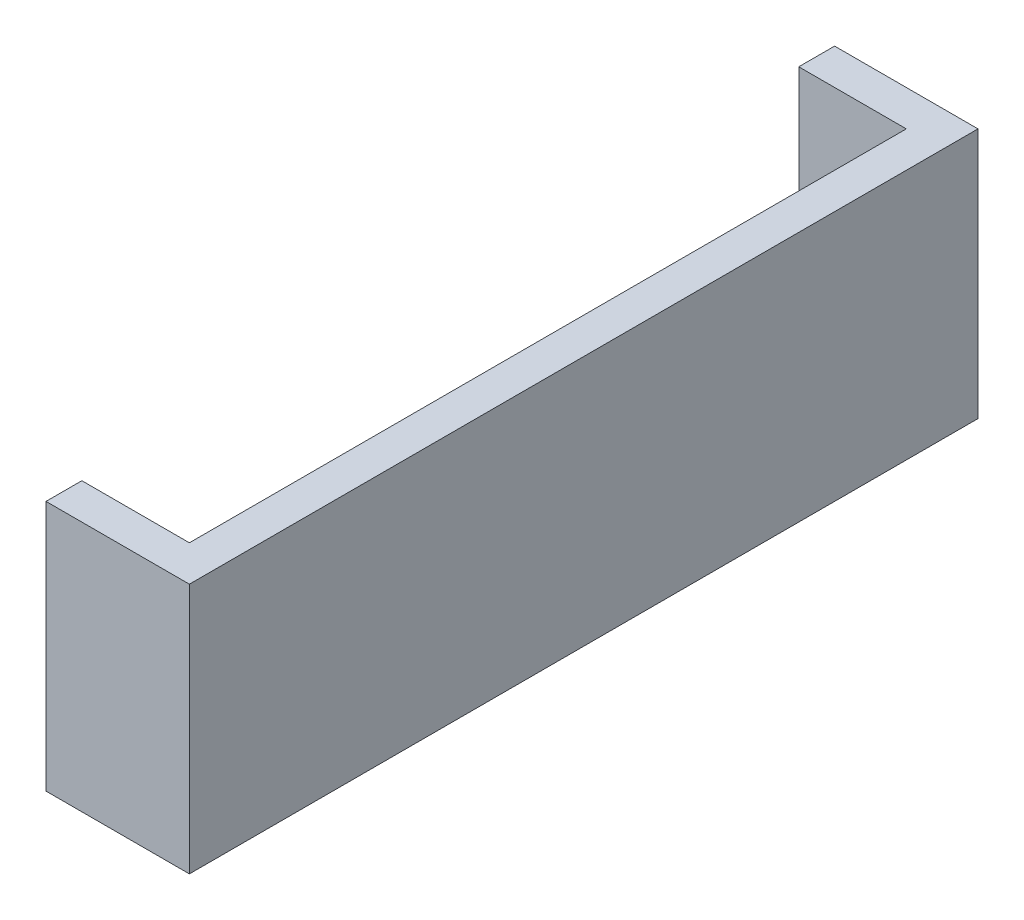
SolidWorks part; units mm, degrees
ref_plane "Front Plane" through (0, 0, 0) normal (0, 0, 1) x (1, 0, 0)
ref_plane "Top Plane" through (0, 0, 0) normal (0, 1, 0) x (1, 0, 0)
ref_plane "Right Plane" through (0, 0, 0) normal (1, 0, 0) x (0, 0, -1)
sketch "Sketch1" plane through (0, 0, 0) normal (0, 1, 0) x (1, 0, 0)
  line L1 (-12.7, -69.85) -> (12.7, -69.85)
  line L2 (-12.7, -69.85) -> (-12.7, 69.85)
  line L3 (-12.7, 69.85) -> (12.7, 69.85)
  line L4 (12.7, -69.85) -> (12.7, 69.85)
  line L5 (-12.7, -69.85) -> (12.7, 69.85) construction
  line L6 (-12.7, 69.85) -> (12.7, -69.85) construction
  point P0 (0, 0)
  dimension "D1" = 25.4
  dimension "D2" = 139.7
extrude "Boss-Extrude1" add sketch "Sketch1" along normal blind 6.35
sketch "Sketch3" plane through (0, 6.35, 0) normal (0, 1, 0) x (1, 0, 0)
  line L0 (12.7, -69.85) -> (12.7, 69.85) construction
  line L1 (-12.7, 69.85) -> (12.7, 69.85)
  line L2 (-12.7, 69.85) -> (-12.7, 63.5)
  line L3 (-12.7, 63.5) -> (12.7, 63.5)
  line L4 (12.7, 69.85) -> (12.7, 63.5)
  line L6 (-12.7, -69.85) -> (12.7, -69.85)
  line L7 (-12.7, -69.85) -> (-12.7, -63.5)
  line L8 (-12.7, -63.5) -> (12.7, -63.5)
  line L9 (12.7, -69.85) -> (12.7, -63.5)
  dimension "D1" = 6.35
extrude "Boss-Extrude2" add sketch "Sketch3" along normal blind 38.1
sketch "Sketch6" plane through (0, 6.35, 0) normal (0, 1, 0) x (1, 0, 0)
  line L0 (12.7, -63.5) -> (12.7, 63.5) construction
  line L1 (12.7, 50.8) -> (19.05, 50.8)
  line L2 (12.7, 50.8) -> (12.7, 38.1)
  line L3 (12.7, 38.1) -> (19.05, 38.1)
  line L5 (12.7, 69.85) -> (-12.7, 69.85) construction
  line L6 (19.05, 57.15) -> (25.4, 57.15)
  line L7 (19.05, 57.15) -> (19.05, 50.8)
  line L8 (19.05, 31.75) -> (25.4, 31.75)
  line L9 (25.4, 57.15) -> (25.4, 31.75)
  line L10 (19.05, 38.1) -> (19.05, 31.75)
  point P10 (25.4, 44.45)
  point P11 (12.7, 44.45)
  dimension "D1" = 6.35
  dimension "D2" = 12.7
  dimension "D3" = 25.4
  dimension "D4" = 6.35
  dimension "D5" = 25.4
extrude "Boss-Extrude3" add sketch "Sketch6" against normal up to surface (6.35 mm away) up to face at (0, 0, 0)
sketch "Sketch7" plane through (0, 6.35, 0) normal (0, 1, 0) x (1, 0, 0)
  line L0 (-12.7, 63.5) -> (-12.7, -63.5) construction
  line L1 (-12.7, 50.8) -> (-6.35, 50.8)
  line L2 (-12.7, 50.8) -> (-12.7, 38.1)
  line L3 (-12.7, 38.1) -> (-6.35, 38.1)
  line L5 (-6.35, 38.1) -> (-6.35, 31.75)
  line L6 (0, 57.15) -> (-6.35, 57.15)
  line L7 (0, 57.15) -> (0, 31.75)
  line L8 (0, 31.75) -> (-6.35, 31.75)
  line L9 (-6.35, 57.15) -> (-6.35, 50.8)
  line L10 (19.05, 50.8) -> (12.7, 50.8) construction
  line L11 (25.4, 57.15) -> (19.05, 57.15) construction
  line L12 (19.05, 57.15) -> (19.05, 50.8) construction
  line L13 (25.4, 31.75) -> (25.4, 57.15) construction
extrude "Cut-Extrude2" cut sketch "Sketch7" against normal through all
mirror "Mirror1" about plane through (0, 0, 0) normal (0, 0, 1) of "Boss-Extrude3", "Cut-Extrude2"
sketch "Sketch8" plane through (0, 6.35, 0) normal (0, 1, 0) x (1, 0, 0)
  line L0 (-12.7, -69.85) -> (12.7, -69.85) construction
  line L1 (12.7, 69.85) -> (25.4, 69.85)
  line L2 (12.7, 69.85) -> (12.7, -69.85)
  line L3 (12.7, -69.85) -> (25.4, -69.85)
  line L4 (25.4, 69.85) -> (25.4, -69.85)
  line L5 (25.4, 31.75) -> (25.4, 57.15) construction
extrude "Cut-Extrude3" cut sketch "Sketch8" against normal through all
sketch "Sketch9" plane through (0, 6.35, 0) normal (0, 1, 0) x (1, 0, 0)
  line L0 (12.7, -63.5) -> (-12.7, -63.5) construction
  line L1 (12.7, 63.5) -> (6.35, 63.5)
  line L2 (12.7, 63.5) -> (12.7, -63.5)
  line L3 (12.7, -63.5) -> (6.35, -63.5)
  line L4 (6.35, 63.5) -> (6.35, -63.5)
  line L5 (-12.7, -63.5) -> (-12.7, -69.85) construction
extrude "Boss-Extrude4" add sketch "Sketch9" along normal up to surface (38.1 mm away) up to face at (0, 44.45, 66.675)
